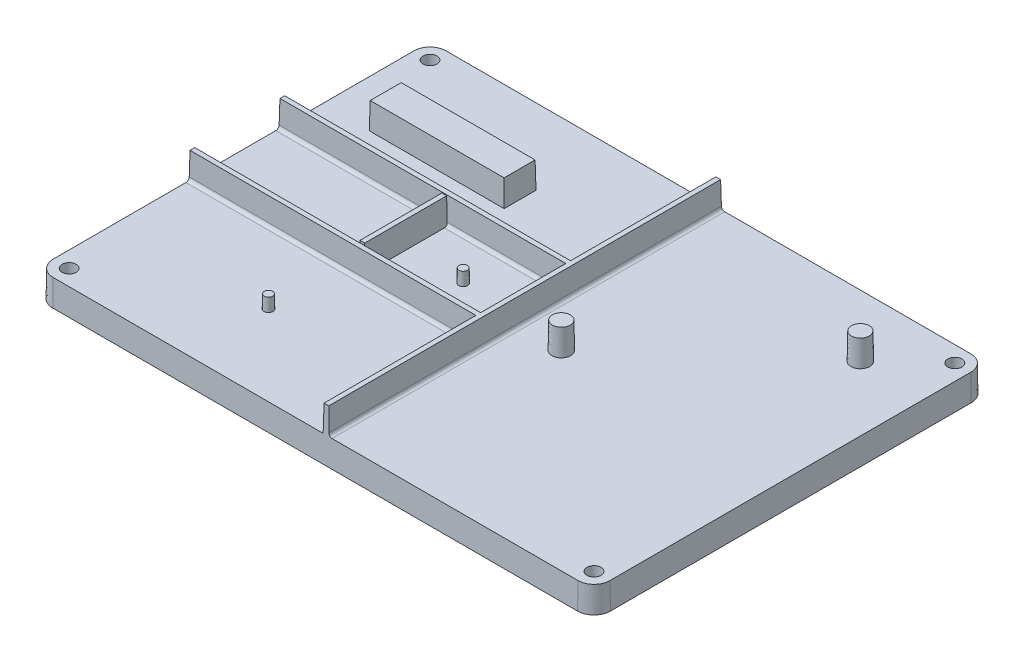
SolidWorks part; units mm, degrees
ref_plane "Front Plane" through (0, 0, 0) normal (0, 0, 1) x (1, 0, 0)
ref_plane "Top Plane" through (0, 0, 0) normal (0, 1, 0) x (1, 0, 0)
ref_plane "Right Plane" through (0, 0, 0) normal (1, 0, 0) x (0, 0, -1)
sketch "Sketch1" plane through (0, 0, 0) normal (0, 1, 0) x (1, 0, 0)
  line L1 (85, -60) -> (-85, -60)
  line L2 (85, -60) -> (85, 60)
  line L3 (85, 60) -> (-85, 60)
  line L4 (-85, -60) -> (-85, 60)
  line L5 (85, -60) -> (-85, 60) construction
  line L6 (85, 60) -> (-85, -60) construction
  point P0 (0, 0)
  dimension "D1" = 170
  dimension "D2" = 120
extrude "Boss-Extrude1" add sketch "Sketch1" along normal blind 8 contours L2 L1 L4 L3
sketch "Sketch2" plane through (-17.7915, 8, -3.068) normal (0, 1, 0) x (1, 0, 0)
  line L1 (-52.8988, 33.84) -> (-11.5182, 33.84)
  line L2 (-52.8988, 33.84) -> (-52.8988, 23.84)
  line L3 (-52.8988, 23.84) -> (-11.5182, 23.84)
  line L4 (-11.5182, 33.84) -> (-11.5182, 23.84)
  line L5 (-52.8988, 33.84) -> (-11.5182, 23.84) construction
  line L6 (-52.8988, 23.84) -> (-11.5182, 33.84) construction
  point P0 (-32.2085, 28.84)
  dimension "D1" = 10
extrude "Boss-Extrude2" add sketch "Sketch2" along normal blind 8 contours L2 L1 L4 L3
sketch "Sketch3" plane through (0, 8, 0) normal (0, 1, 0) x (1, 0, 0)
  line L0 (-85, -60) -> (-85, 60) construction
  line L1 (85, 60) -> (-85, 60) construction
  line L2 (85, -60) -> (-85, -60) construction
  line L3 (85, -60) -> (85, 60) construction
  circle A0 centre (-80, 55) radius 2
  circle A1 centre (-80, -55) radius 2
  circle A2 centre (80, 55) radius 2
  circle A3 centre (80, -55) radius 2
  dimension "D1" = 5
  dimension "D3" = 5
  dimension "D7" = 5
  dimension "D2" = 5
  dimension "D4" = 5
  dimension "D5" = 5
  dimension "D6" = 5
  dimension "D8" = 5
extrude "Cut-Extrude1" cut sketch "Sketch3" against normal blind 8
sketch "Sketch7" plane through (12.7031, 8, 3.5658) normal (0, 1, 0) x (1, 0, 0)
  circle A0 centre (52.4005, 44.6595) radius 3
extrude "Boss-Extrude3" add sketch "Sketch7" along normal blind 8 contours A0
sketch "Sketch8" plane through (0, 16, 3.5658) normal (0, 1, 0) x (1, 0, 0)
  circle A0 centre (65.1036, 44.6595) radius 1.5
extrude "Boss-Extrude6" add sketch "Sketch8" against normal blind 4 contours A0
sketch "Sketch9" plane through (0, 16, 3.5658) normal (0, 1, 0) x (1, 0, 0)
  circle A0 centre (64.9051, 44.2737) radius 1.5
extrude "Boss-Extrude7" add sketch "Sketch9" against normal blind 4
sketch "Sketch10" plane through (-8.7547, 8, 20.4679) normal (0, 1, 0) x (1, 0, 0)
  circle A0 centre (25.4063, 18.8562) radius 3
extrude "Boss-Extrude8" add sketch "Sketch10" along normal blind 8
sketch "Sketch11" plane through (4.1485, 8, 0) normal (0, 1, 0) x (1, 0, 0)
  line L5 (-2, 60) -> (0, 60)
  line L6 (-2, 60) -> (-2, -60)
  line L7 (-2, -60) -> (0, -60)
  line L8 (0, 60) -> (0, -60)
  dimension "D1" = 2
extrude "Boss-Extrude9" add sketch "Sketch11" along normal blind 8
sketch "Sketch13" plane through (0, 8, 0) normal (0, 1, 0) x (1, 0, 0)
  line L0 (-85, -60) -> (-85, 60) construction
  line L1 (-85, 15.6956) -> (2.1485, 15.6956)
  line L2 (-85, 15.6956) -> (-85, 13.6956)
  line L3 (-85, 13.6956) -> (2.1485, 13.6956)
  line L4 (2.1485, 15.6956) -> (2.1485, 13.6956)
  line L5 (2.1485, 60) -> (2.1485, -60) construction
  dimension "D1" = 2
extrude "Boss-Extrude10" add sketch "Sketch13" along normal blind 8 contours L3 L4 L1 L2
extrude "Boss-Extrude11" add sketch "Sketch7<3>" against normal blind 1.2897
sketch "Sketch7<3>" plane through (12.7031, 8, 3.5658) normal (0, 1, 0) x (1, 0, 0) same geometry as "Sketch7"
sketch "Sketch14" plane through (0, 16, 0) normal (0, 1, 0) x (1, 0, 0)
  line L0 (-85, 13.6956) -> (2.1485, 13.6956) construction
  line L1 (-35.3306, 13.6956) -> (-33.3306, 13.6956)
  line L2 (-35.3306, 13.6956) -> (-35.3306, -11.3044)
  line L3 (-35.3306, -11.3044) -> (-33.3306, -11.3044)
  line L4 (-33.3306, 13.6956) -> (-33.3306, -11.3044)
  line L5 (-85, -60) -> (-85, 13.6956) construction
  line L6 (-33.3306, -11.3044) -> (-85, -11.3044)
  line L7 (-33.3306, -11.3044) -> (-33.3306, -13.3044)
  line L8 (-33.3306, -13.3044) -> (-85, -13.3044)
  line L9 (-85, -11.3044) -> (-85, -13.3044)
  dimension "D1" = 2
  dimension "D2" = 25
  dimension "D3" = 2
extrude "Boss-Extrude13" add sketch "Sketch14" against normal blind 8 separate body contours L3 L2 L1 L4
sketch "Sketch18" plane through (0, 8, 0) normal (0, 1, 0) x (1, 0, 0)
  line L0 (2.1485, 13.6956) -> (2.1485, -60) construction
  line L1 (2.1485, -11.7107) -> (-85, -11.7107)
  line L2 (2.1485, -11.7107) -> (2.1485, -13.7107)
  line L3 (2.1485, -13.7107) -> (-85, -13.7107)
  line L4 (-85, -11.7107) -> (-85, -13.7107)
  line L5 (-85, -60) -> (-85, 13.6956) construction
  dimension "D1" = 2
extrude "Boss-Extrude16" add sketch "Sketch18" along normal blind 8 contours L1 L4 L3 L2
sketch "Sketch19" plane through (0, 8, 0) normal (0, 1, 0) x (1, 0, 0)
  circle A0 centre (-16.0623, 1.1849) radius 1.5
  circle A1 centre (-38.9018, -35.3306) radius 1.5
extrude "Boss-Extrude17" add sketch "Sketch19" along normal blind 4
draft "Draft3" type of draft neutral plane draft angle 1 neutral plane "Top Plane" faces to draft 20 face at (-16.0623, 12, 0.3151) face at (80, 0, -53) face at (-80, 0, -53) face at (80, 0, 57) face at (-80, 0, 57) face at (4.1485, 12, 0) face at (-29.3097, 12, -31.9081) face at (-50, 12, -26.9081) face at (-70.6903, 12, -31.9081) face at (-50, 12, -36.9081) face at (-38.9018, 12, 36.8306) face at (16.6516, 16, 4.6117) face at (65.1036, 16, -38.0937) face at (-41.4257, 12, -13.6956) face at (-41.4257, 12, -15.6956) face at (-41.4257, 12, 11.7107) face at (-41.4257, 12, 13.7107) face at (2.1485, 12, 36.8554) face at (2.1485, 12, -0.9924) face at (2.1485, 12, -37.8478) neutral plane through (0, 0, 0) neutral plane normal (0, 1, 0) parameters "D1"=1
fillet "Fillet1" radius 1 7 edges at (-41.3559, 8, 13.5711) (-41.3559, 8, 11.8504) (-41.3559, 8, -13.8352) (2.2881, 8, -0.9924) (4.0089, 8, 0) (2.2881, 8, -37.778) (-41.3559, 8, -15.5559)
fillet "Fillet6" radius 5 4 edges at (85, 4, -60) (85, 4, 60) (-85, 4, 60) (-85, 4, -60)
draft "Draft1" type of draft neutral plane draft angle 1 neutral plane "Top Plane" faces to draft 8 face at (83.0178, 4, 58.0178) face at (85, 4, 0) face at (83.0178, 4, -58.0178) face at (1.8891, 8.1556, -60) face at (-83.0178, 4, -58.0178) face at (-83.0178, 4, 58.0178) face at (-85, 9.1945, -0.7443) face at (1.9297, 8.0864, 60) neutral plane through (0, 0, 0) neutral plane normal (0, 1, 0) reverse direction yes parameters "D1"=1
draft "Draft2" type of draft neutral plane draft angle 1 neutral plane "Top Plane" faces to draft 8 face at (83.0599, 4, -58.0599) face at (85.0698, 4, 0) face at (83.0599, 4, 58.0599) face at (1.9297, 8.0864, 60.1411) face at (-83.0599, 4, 58.0599) face at (-85.1605, 9.1945, -0.7443) face at (-83.0599, 4, -58.0599) face at (1.8891, 8.1556, -60.1424) neutral plane through (0, 0, 0) neutral plane normal (0, 1, 0) parameters "D1"=1
draft "Draft4" type of draft neutral plane draft angle 1 neutral plane "Top Plane" faces to draft 2 face at (-35.3306, 12, -1.1956) face at (-33.3306, 12, -1.1956) neutral plane through (0, 0, 0) neutral plane normal (0, 1, 0) parameters "D1"=1
